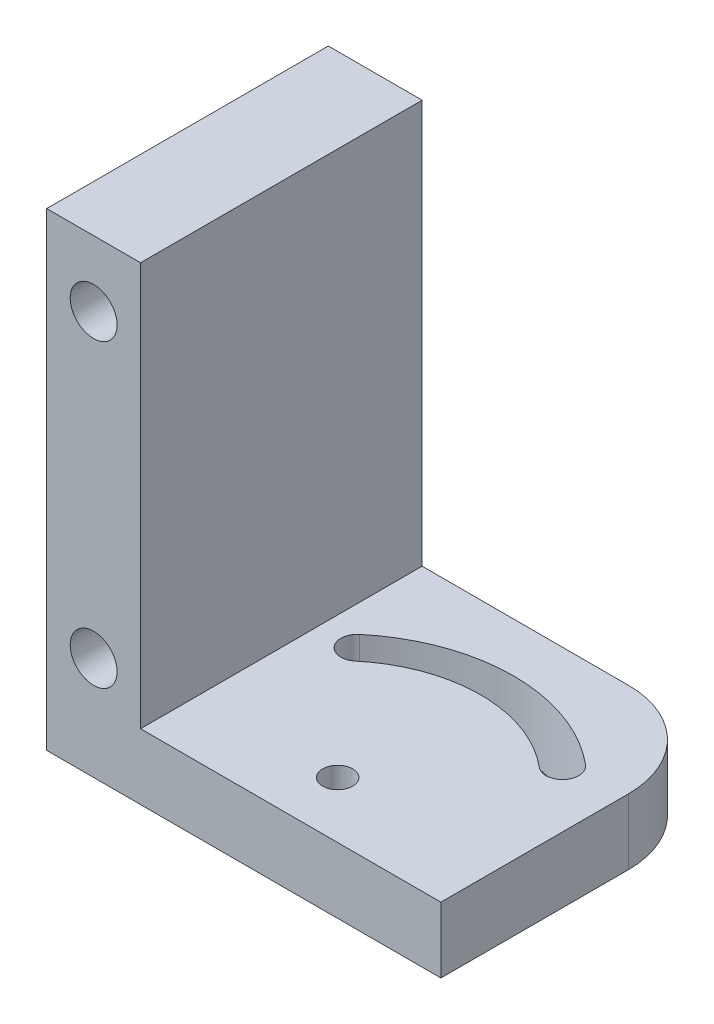
SolidWorks part; units mm, degrees
ref_plane "Front" through (0, 0, 0) normal (0, 0, 1) x (1, 0, 0)
ref_plane "Top" through (0, 0, 0) normal (0, 1, 0) x (1, 0, 0)
ref_plane "Right" through (0, 0, 0) normal (1, 0, 0) x (0, 0, -1)
sketch "Sketch1" plane through (0, 0, 0) normal (0, 1, 0) x (1, 0, 0)
  line L0 (-9.2209, -2.1089) -> (1.7065, -15.1317) construction
  line L1 (-23.2935, 8.8683) -> (1.7065, 8.8683)
  line L2 (-23.2935, 8.8683) -> (-23.2935, -21.1317)
  line L3 (-23.2935, -21.1317) -> (1.7065, -21.1317)
  line L4 (1.7065, 8.8683) -> (1.7065, -21.1317) construction
  line L5 (1.7065, -15.1317) -> (12.6339, -2.1089) construction
  line L7 (1.7065, -21.1317) -> (18.7065, -21.1317)
  line L8 (1.7065, -21.1317) -> (1.7065, 8.8683) construction
  line L9 (1.7065, 8.8683) -> (8.7065, 8.8683)
  line L10 (18.7065, -21.1317) -> (18.7065, -1.1317)
  line L11 (-23.2935, -21.1317) -> (-13.2935, -21.1317)
  line L12 (-23.2935, -21.1317) -> (-23.2935, 8.8683)
  line L13 (-23.2935, 8.8683) -> (-13.2935, 8.8683)
  line L14 (-13.2935, -21.1317) -> (-13.2935, 8.8683)
  circle A0 centre (1.7065, -15.1317) radius 1.6
  arc A1 (12.6339, -2.1089) -> (-9.2209, -2.1089) centre (1.7065, -15.1317) ccw construction
  arc A2 (-9.2209, -2.1089) -> (12.6339, -2.1089) centre (1.7065, -15.1317) cw construction
  arc A3 (13.7588, -0.7683) -> (-10.3457, -0.7683) centre (1.7065, -15.1317) ccw
  arc A4 (11.509, -3.4495) -> (-8.096, -3.4495) centre (1.7065, -15.1317) ccw
  arc A5 (11.509, -3.4495) -> (13.7588, -0.7683) centre (12.6339, -2.1089) ccw
  arc A6 (-10.3457, -0.7683) -> (-8.096, -3.4495) centre (-9.2209, -2.1089) ccw
  arc A7 (18.7065, -1.1317) -> (8.7065, 8.8683) centre (8.7065, -1.1317) ccw
  point P9 (1.7065, 1.8683)
  point P20 (0, 0)
  dimension "D3" = 3.2
  dimension "D4" = 6
  dimension "D5" = 40
  dimension "D6" = 3.5
  dimension "D7" = 17
  dimension "D8" = 10
  dimension "D1" = 30
  dimension "D2" = 25
  dimension "D9" = 10
  dimension "D10" = 17
  dimension "D11" = 40
extrude "Boss-Extrude1" add sketch "Sketch1" along normal blind 7 contours L3 L14 L1 L2 | L10 A7 L9 L1 L14 L3 L7 A0 A6 A3 A5 A4 region at (-18.2935, 0, 6.1317) region at (2.4742, 0, 7.0781)
extrude "Boss-Extrude2" add sketch "Sketch1<3>" along normal blind 50 contours L3 L14 L1 L2 region at (-18.2935, 0, 6.1317)
sketch "Sketch1<3>" plane through (0, 0, 0) normal (0, 1, 0) x (1, 0, 0) same geometry as "Sketch1"
sketch "Sketch2" plane through (0, 0, -8.8683) normal (0, 0, -1) x (-1, 0, 0)
  line L0 (23.2935, 43) -> (13.2935, 43) construction
  line L1 (23.2935, 50) -> (23.2935, 0) construction
  line L2 (13.2935, 50) -> (13.2935, 7) construction
  line L3 (23.2935, 50) -> (13.2935, 50) construction
  circle A0 centre (18.2935, 43) radius 2.5
  circle A1 centre (18.2935, 11) radius 2.5
  point P2 (0, 0)
  dimension "D1" = 5
  dimension "D2" = 7
  dimension "D3" = 32
extrude "Cut-Extrude1" cut sketch "Sketch2" against normal through all
